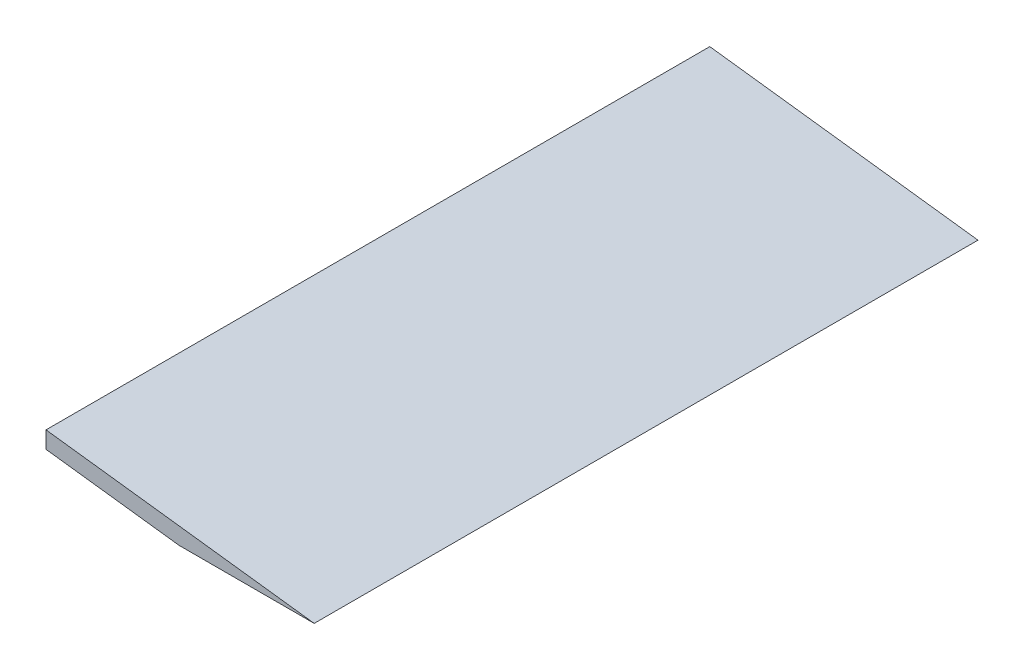
SolidWorks part; units mm, degrees
ref_plane "Front Plane" through (0, 0, 0) normal (0, 0, 1) x (1, 0, 0)
ref_plane "Top Plane" through (0, 0, 0) normal (0, 1, 0) x (1, 0, 0)
ref_plane "Right Plane" through (0, 0, 0) normal (1, 0, 0) x (0, 0, -1)
sketch "Sketch1" plane through (0, 0, 0) normal (0, 0, 1) x (1, 0, 0)
  line L0 (0, 0) -> (50.8, -6.35)
  line L1 (50.8, -6.35) -> (25.2023, -6.35)
  line L2 (25.2023, -6.35) -> (0, -3.1997)
  line L3 (0, -3.1997) -> (0, 0)
  point P3 (0, 0)
  point P6 (17.4792, -6.35)
  dimension "D1" = 6.35
  dimension "D2" = 3.175
  dimension "D3" = 50.8
  dimension "D4" = 7.125
  dimension "D5" = 82.875
extrude "Boss-Extrude1" add sketch "Sketch1" along normal blind 125.73
